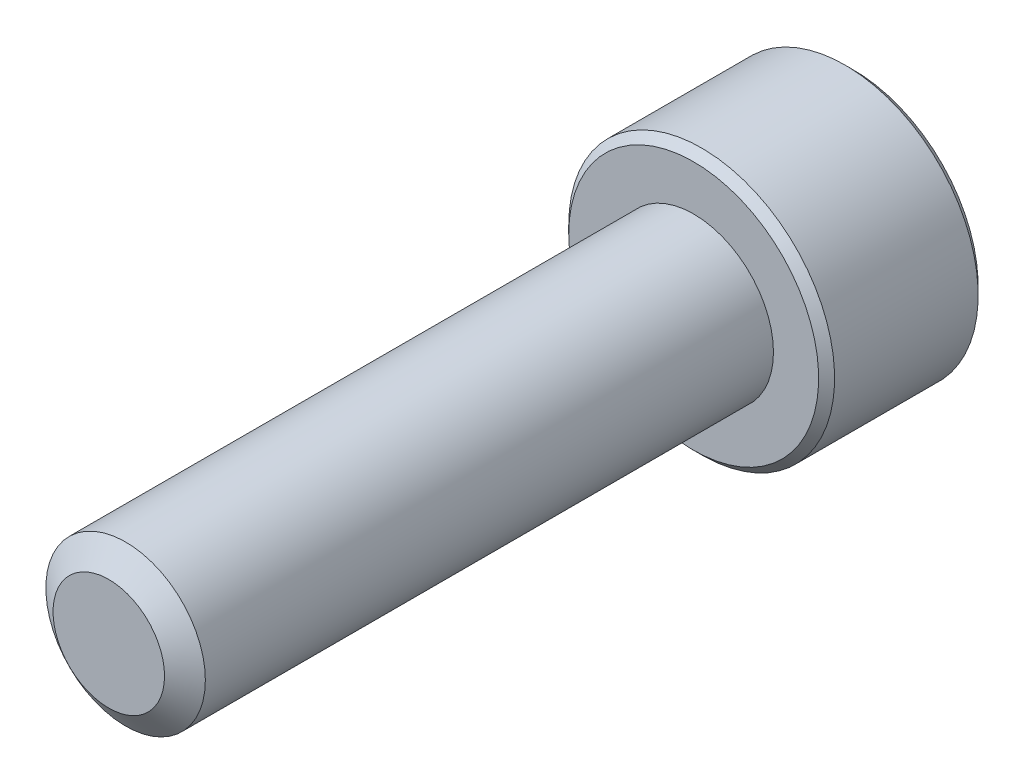
SolidWorks part; units mm, degrees
material "Alloy Steel"
ref_plane "Front Plane" through (0, 0, 0) normal (0, 0, 1) x (1, 0, 0)
ref_plane "Top Plane" through (0, 0, 0) normal (0, 1, 0) x (1, 0, 0)
ref_plane "Right Plane" through (0, 0, 0) normal (1, 0, 0) x (0, 0, -1)
sketch "Sketch1" plane through (0, 0, 0) normal (0, 0, 1) x (1, 0, 0)
  circle A0 centre (0, 0) radius 3
  dimension "OD" = 6
extrude "Extrude1" add sketch "Sketch1" against normal blind 22
sketch "Sketch2" plane through (0, 0, 0) normal (0, 0, 1) x (1, 0, 0)
  circle A0 centre (0, 0) radius 3 construction
  circle A1 centre (0, 0) radius 3
curve "Helix/Spiral1" pitch 1 height 23 turns 23 parameters "pitch"=1
sketch "Sketch3" plane through (0, 0, 0) normal (1, 0, 0) x (0, 0, -1)
  line L0 (-0.875, 3) -> (-0.5, 2.3505)
  line L1 (-0.5, 2.3505) -> (-0.375, 2.3505)
  line L2 (-0.375, 2.3505) -> (0, 3)
  line L3 (-0.875, 3) -> (0, 3)
  line L4 (-0.4375, 3) -> (-0.4375, 2.3505) construction
  line L5 (-0.6875, 2.6752) -> (-0.1875, 2.6752) construction
  line L6 (0, 3) -> (0, -3) construction
  line L7 (0, -3) -> (22, -3) construction
  point P11 (4.5, -3)
  dimension "D1" = 0.125
  dimension "D2" = 0.5
  dimension "D3" = 60
  dimension "D4" = 4.5
sweep "Cut-Sweep1" [suppressed] cut profiles "Sketch3" path "Helix/Spiral1"
sketch "Sketch4" plane through (0, 0, 0) normal (1, 0, 0) x (0, 0, -1)
  line L0 (0.6327, 3) -> (0, 2.0965)
  line L1 (0, 2.0965) -> (0, 3)
  line L2 (0.6327, 3) -> (0, 3)
  line L3 (-0.875, 3) -> (0, 3) construction
  line L4 (0, 0) -> (7.0209, 0) construction
  dimension "D1" = 55
  dimension "D2" = 0.254
revolve "Cut-Revolve1" cut sketch "Sketch4" angle 360 about L4
sketch "Sketch5" [suppressed] plane through (0, 0, 0) normal (1, 0, 0) x (0, 0, -1)
  line L0 (22, -2.3644) -> (22, 2.1406) construction
  line L1 (22, 3) -> (0.1203, 3)
  line L2 (22, 3) -> (22, 0)
  line L3 (22, 0) -> (0.0001, 0)
  line L4 (0.0001, 2.6698) -> (0.0001, 0)
  line L5 (0.1203, 3) -> (0.0001, 2.6698)
  line L6 (0, 0) -> (9.9695, 0) construction
  point P3 (0.0001, 3)
  point P10 (0.0001, 3)
  dimension "D1" = 0.3302
  dimension "Thread min" = 0.0001
  dimension "D3" = 20
revolve "partially thread" [suppressed] add sketch "Sketch5" angle 360 about L6
sketch "Sketch6" plane through (0, 0, -22) normal (0, 0, -1) x (-1, 0, 0)
  circle A0 centre (0, 0) radius 5
  dimension "head dia" = 10
extrude "Extrude2" add sketch "Sketch6" along normal blind 6
sketch "Sketch7" plane through (0, 0, -28) normal (0, 0, -1) x (-1, 0, 0)
  line L1 (0, 2.8868) -> (-2.5, 1.4434)
  line L2 (-2.5, 1.4434) -> (-2.5, -1.4434)
  line L3 (-2.5, -1.4434) -> (0, -2.8868)
  line L4 (0, -2.8868) -> (2.5, -1.4434)
  line L5 (2.5, -1.4434) -> (2.5, 1.4434)
  line L6 (2.5, 1.4434) -> (0, 2.8868)
  circle A0 centre (0, 0) radius 2.5 construction
  dimension "hex dia" = 5
extrude "Cut-Extrude1" cut sketch "Sketch7" against normal blind 3.75
sketch "Sketch8" plane through (0, 0, -28) normal (0, 0, -1) x (-1, 0, 0)
  circle A0 centre (0, 0) radius 2.8868
extrude "Cut-Extrude2" cut sketch "Sketch8" against normal through all draft 45
chamfer "Chamfer1" distance 0.3 angle 45 2 edges at (-5, 0, -28) (-5, 0, -22)
sketch "Sketch9" plane through (0, 0, 0) normal (1, 0, 0) x (0, 0, -1)
  line L0 (0, 3) -> (0, -3) construction
  line L1 (5.5, 3) -> (5.5, -3) construction
  dimension "D1" = 5.5
sketch "Sketch10" plane through (0, 0, 0) normal (1, 0, 0) x (0, 0, -1)
  line L0 (22, 3) -> (22, 0)
  line L1 (22, 3) -> (21.75, 3)
  line L2 (21.75, 3) -> (20.5074, 0)
  line L3 (22, 0) -> (20.5074, 0)
  line L4 (22, 4.7) -> (22, -4.7) construction
  dimension "D1" = 22.5
  dimension "D2" = 0.25
revolve "Revolve1" add sketch "Sketch10" angle 360 about L3
equation "\"D3@Helix/Spiral1\" = \"screw length@Extrude1\"+\"pitch@Helix/Spiral1\""
equation "\"D1@Sketch3\" = \"pitch@Helix/Spiral1\"*.125"
equation "\"D2@Sketch3\" = \"pitch@Helix/Spiral1\"*.5"
equation "\"D1@Cut-Extrude1\" = \"hex dia@Sketch7\"*.75"
equation "\"D1@Chamfer1\" = \"head dia@Sketch6\"*.03"
equation "\"D1@Sketch9\" = \"pitch@Helix/Spiral1\"*5.5"
equation "\"D2@Sketch10\" = \"pitch@Helix/Spiral1\"*.25"
equation "\"D4@Sketch3\" = \"pitch@Helix/Spiral1\"*4.50"
